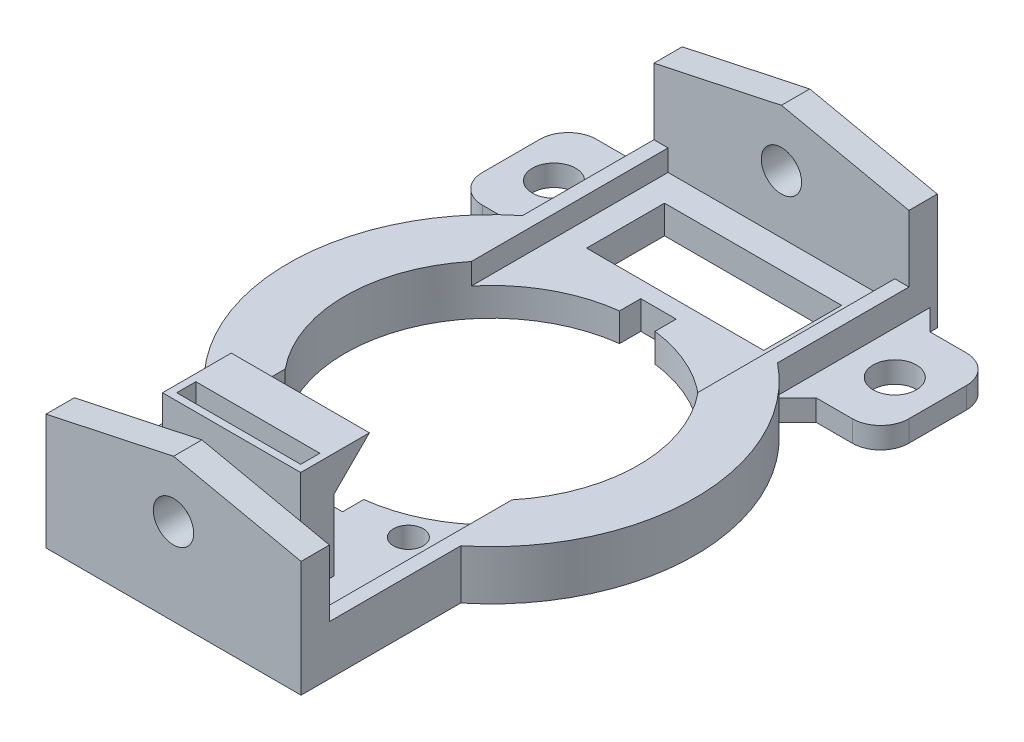
SolidWorks part; units mm, degrees
ref_plane "Front Plane" through (0, 0, 0) normal (0, 0, 1) x (1, 0, 0)
ref_plane "Top Plane" through (0, 0, 0) normal (0, 1, 0) x (1, 0, 0)
ref_plane "Right Plane" through (0, 0, 0) normal (1, 0, 0) x (0, 0, -1)
sketch "Sketch1" plane through (0, 0, 0) normal (0, 0, 1) x (1, 0, 0)
  line L3 (-18, 114.7896) -> (0, 114.7896)
  line L4 (0, 114.7896) -> (18, 114.7896)
  line L7 (0, 118.6383) -> (-38.0273, 110.5073) construction
  line L9 (38.0273, 110.5073) -> (0, 118.6383) construction
  line L11 (18, 114.7896) -> (18, 121.7896)
  line L12 (18, 121.7896) -> (16, 121.7896)
  line L13 (16, 121.7896) -> (16, 118.7896)
  line L14 (16, 118.7896) -> (-16, 118.7896)
  line L15 (-16, 118.7896) -> (-16, 121.7896)
  line L16 (-16, 121.7896) -> (-18, 121.7896)
  line L17 (-18, 121.7896) -> (-18, 114.7896)
  point P15 (0, 118.7896)
  dimension "D1" = 32
  dimension "D2" = 2
  dimension "D3" = 3
  dimension "D4" = 4
extrude "Boss-Extrude1" add sketch "Sketch1" along normal up to surface (89.8 mm away)
sketch "Sketch2" plane through (0, 114.7896, 0) normal (0, -1, 0) x (1, 0, 0)
  line L0 (18, 89.8) -> (18, 0) construction
  line L5 (-14, 54.9) -> (14, 54.9)
  line L6 (-14, 54.9) -> (-14, 34.9)
  line L7 (-14, 34.9) -> (14, 34.9)
  line L8 (14, 54.9) -> (14, 34.9)
  point P4 (0, 34.9)
  point P8 (18, 44.9)
  point P9 (14, 44.9)
  dimension "D1" = 4
  dimension "D2" = 20
extrude "Cut-Extrude1" [suppressed] cut sketch "Sketch2" against normal up to next
sketch "Sketch3" plane through (-18, 0, 0) normal (-1, 0, 0) x (0, 0, 1)
  line L0 (89.8, 121.7896) -> (0, 121.7896) construction
  line L1 (40.65, 118.7896) -> (49.15, 118.7896)
  line L2 (40.65, 118.7896) -> (40.65, 121.7896)
  line L3 (40.65, 121.7896) -> (49.15, 121.7896)
  line L4 (49.15, 118.7896) -> (49.15, 121.7896)
  line L5 (89.8, 118.7896) -> (0, 118.7896) construction
  point P9 (44.9, 121.7896)
  point P10 (44.9, 121.7896)
  dimension "D1" = 8.5
extrude "Cut-Extrude2" [suppressed] cut sketch "Sketch3" against normal through all
sketch "Sketch4" plane through (0, 118.7896, 0) normal (0, 1, 0) x (1, 0, 0)
  circle A0 centre (7.75, -23.25) radius 2.1 construction
  circle A4 centre (-7.75, -23.25) radius 2.1 construction
  circle A5 centre (7.75, -23.25) radius 2.1
  circle A6 centre (-7.75, -23.25) radius 2.1
extrude "Cut-Extrude3" [suppressed] cut sketch "Sketch4" against normal through all
ref_plane "Plane2" through (0, 0, 44.9) normal (0, 0, -1) x (-1, 0, 0)
sketch "Sketch5" plane through (0, 0, 0) normal (0, 0, 1) x (1, 0, 0)
  line L0 (-18, 114.7896) -> (-18, 131.1512)
  line L1 (-56.4, 122.9405) -> (0, 135) construction
  line L2 (-18, 131.1512) -> (0, 135)
  line L3 (0, 135) -> (18, 131.1512)
  line L4 (0, 135) -> (56.4, 122.9405) construction
  line L5 (18, 131.1512) -> (18, 114.7896)
  line L6 (18, 114.7896) -> (-18, 114.7896)
  line L7 (0.6273, 134.8659) -> (54.0273, 123.4479) construction
  line L8 (-54.0273, 123.4479) -> (-0.6273, 134.8659) construction
  circle A0 centre (0, 127) radius 2.85
  dimension "D1" = 5.7
  dimension "D2" = 8
extrude "Boss-Extrude2" add sketch "Sketch5" along normal blind 4
mirror "Mirror1" about plane through (0, 0, 44.9) normal (0, 0, -1) of "Boss-Extrude2"
sketch "Sketch6" plane through (0, 118.7896, 0) normal (0, 1, 0) x (1, 0, 0)
  line L1 (12.5, -19) -> (-12.5, -19)
  line L2 (12.5, -19) -> (12.5, -8)
  line L3 (12.5, -8) -> (-12.5, -8)
  line L4 (-12.5, -19) -> (-12.5, -8)
  point P4 (0, -8)
  dimension "D1" = 11
  dimension "D2" = 25
  dimension "D3" = 8
extrude "Cut-Extrude4" cut sketch "Sketch6" against normal through all
sketch "Sketch8" plane through (0, 118.7896, 0) normal (0, 1, 0) x (1, 0, 0)
  line L0 (16, -85.8) -> (-16, -85.8) construction
  line L1 (8.75, -80.6) -> (-8.75, -80.6)
  line L2 (8.75, -80.6) -> (8.75, -77.9)
  line L3 (8.75, -77.9) -> (-8.75, -77.9)
  line L4 (-8.75, -80.6) -> (-8.75, -77.9)
  line L5 (0, -89.8) -> (53.4, -89.8) construction
  line L6 (9.75, -76.9) -> (-9.75, -76.9)
  line L7 (-9.75, -81.6) -> (-9.75, -76.9)
  line L8 (9.75, -81.6) -> (-9.75, -81.6)
  line L9 (9.75, -81.6) -> (9.75, -76.9)
  point P6 (0, -85.8)
  point P7 (0, -80.6)
  dimension "D1" = 8.2
  dimension "D2" = 2.7
  dimension "D3" = 17.5
  dimension "D4" = 1
extrude "Boss-Extrude3" add sketch "Sketch8" along normal blind 15
sketch "Sketch9" plane through (-9.75, 0, 0) normal (-1, 0, 0) x (0, 0, 1)
  line L0 (76.9, 128.7896) -> (71.9, 133.7896)
  line L1 (76.9, 133.7896) -> (76.9, 118.7896) construction
  line L2 (71.9, 133.7896) -> (76.9, 133.7896)
  line L3 (76.9, 133.7896) -> (76.9, 128.7896)
  dimension "D1" = 5
  dimension "D2" = 45
extrude "Boss-Extrude4" add sketch "Sketch9" against normal up to surface (19.5 mm away) up to face at (9.75, 126.2896, 79.25)
sketch "Sketch13" plane through (0, 118.7896, 0) normal (0, 1, 0) x (1, 0, 0)
  line L4 (-8.75, -80.6) -> (8.75, -80.6)
  line L5 (8.75, -80.6) -> (8.75, -77.9)
  line L6 (8.75, -77.9) -> (-8.75, -77.9)
  line L7 (-8.75, -77.9) -> (-8.75, -80.6)
  line L8 (-8.75, -80.6) -> (8.75, -80.6)
  line L9 (8.75, -80.6) -> (8.75, -77.9)
  line L10 (8.75, -77.9) -> (-8.75, -77.9)
  line L11 (-8.75, -77.9) -> (-8.75, -80.6)
  dimension "D1" = 0
extrude "Cut-Extrude5" cut sketch "Sketch13" against normal through all
sketch "Sketch10" [suppressed] plane through (0, 121.7896, 0) normal (0, 1, 0) x (1, 0, 0)
  line L1 (16, -59.15) -> (18, -59.15)
  line L2 (16, -59.15) -> (16, -49.15)
  line L3 (16, -49.15) -> (18, -49.15)
  line L4 (18, -59.15) -> (18, -49.15)
  line L5 (0, -1000) -> (0, 49000) construction
  line L6 (-16, -49.15) -> (-18, -49.15)
  line L7 (-16, -59.15) -> (-16, -49.15)
  line L8 (-16, -59.15) -> (-18, -59.15)
  line L9 (-18, -59.15) -> (-18, -49.15)
  dimension "D1" = 10
extrude "Boss-Extrude5" [suppressed] add sketch "Sketch10" along normal up to surface (12 mm away)
sketch "Sketch14" plane through (0, 114.7896, 0) normal (0, 1, 0) x (1, 0, 0)
  line L0 (-18, -85.8) -> (-18, -4) construction
  line L1 (-18, -4) -> (-30.1, -4)
  line L2 (-18, -4) -> (-18, -20.1)
  line L3 (-18, -20.1) -> (-30.1, -20.1)
  line L4 (-30.1, -4) -> (-30.1, -20.1)
  circle A0 centre (-24.05, -12.05) radius 3.05
  point P9 (-30.1, -12.05)
  point P10 (-24.05, -20.1)
  dimension "D1" = 6.1
  dimension "D2" = 3
  dimension "D3" = 5
extrude "Boss-Extrude7" add sketch "Sketch14" along normal blind 3
mirror "Mirror2" about plane through (0, 0, 0) normal (1, 0, 0) of "Boss-Extrude7"
chamfer "Chamfer1" distance 3 angle 45 4 edges at (-18, 116.2896, 20.1) (-18, 116.2896, 4) (18, 116.2896, 4) (18, 116.2896, 20.1)
sketch "Sketch17" plane through (0, 118.7896, 0) normal (0, 1, 0) x (1, 0, 0)
  circle A0 centre (0, -71.9) radius 2.1
  circle A1 centre (0, -71.9) radius 2.85 construction
  dimension "D1" = 4.2
extrude "Cut-Extrude6" cut sketch "Sketch17" against normal through all
sketch "Sketch19" plane through (0, 114.7896, 0) normal (0, -1, 0) x (1, 0, 0)
  line L0 (18, 67.2537) -> (18, 55.122)
  line L2 (-16, 68.7262) -> (-16, 58.0335)
  line L3 (-18, 34.678) -> (-18, 22.5463)
  line L4 (18, 22.5463) -> (18, 34.678)
  line L6 (-18, 85.8) -> (-18, 4) construction
  line L7 (18, 85.8) -> (18, 4) construction
  line L8 (-16, 85.8) -> (-16, 4) construction
  arc A0 (-16, 58.0335) -> (-18, 34.678) centre (0, 44.9) ccw
  arc A1 (-16, 68.7262) -> (-18, 22.5463) centre (0, 44.9) ccw
  circle A2 centre (0, 44.9) radius 20.2 construction
  arc A3 (18, 22.5463) -> (18, 67.2537) centre (0, 44.9) ccw
  arc A4 (18, 34.678) -> (18, 55.122) centre (0, 44.9) ccw
  dimension "D1" = 0.5
  dimension "D2" = 8
extrude "Boss-Extrude8" add sketch "Sketch19" against normal up to surface (7 mm away) up to face at (-17, 121.7896, 44.9)
sketch "Sketch20" plane through (0, 114.7896, 0) normal (0, -1, 0) x (1, 0, 0)
  circle A0 centre (0, 44.9) radius 20.7
  arc A1 (18, 34.678) -> (18, 55.122) centre (0, 44.9) ccw construction
extrude "Cut-Extrude7" cut sketch "Sketch20" against normal through all
fillet "Fillet1" radius 4 4 edges at (-30.1, 116.2896, 4) (-30.1, 116.2896, 20.1) (30.1, 116.2896, 4) (30.1, 116.2896, 20.1)
sketch "Sketch21" plane through (0, 118.7896, 0) normal (0, 1, 0) x (1, 0, 0)
  circle A0 centre (-10.2696, -66.9233) radius 2.1 construction
  circle A1 centre (10.2696, -66.9233) radius 2.1 construction
  circle A2 centre (-10.2696, -66.9233) radius 2.1
  circle A3 centre (10.2696, -66.9233) radius 2.1
extrude "Cut-Extrude8" cut sketch "Sketch21" against normal through all
sketch "Sketch22" plane through (0, 118.7896, 0) normal (0, 1, 0) x (1, 0, 0)
  line L0 (-1000, -44.9) -> (49000, -44.9) construction
  line L1 (-2.5, -65.4485) -> (2.5, -65.4485)
  line L2 (-2.5, -65.4485) -> (-2.5, -68.4485)
  line L3 (-2.5, -68.4485) -> (2.5, -68.4485)
  line L4 (2.5, -65.4485) -> (2.5, -68.4485)
  line L5 (2.5, -24.3515) -> (2.5, -21.3515)
  line L6 (-2.5, -21.3515) -> (2.5, -21.3515)
  line L7 (-2.5, -24.3515) -> (-2.5, -21.3515)
  line L8 (-2.5, -24.3515) -> (2.5, -24.3515)
  arc A0 (-16, -58.0335) -> (16, -58.0335) centre (0, -44.9) ccw construction
  dimension "D1" = 5
  dimension "D2" = 3
extrude "Cut-Extrude9" cut sketch "Sketch22" against normal through all
equation "\"width\"= 24"
equation "\"thk\"= 3"
equation "\"holesize\"= 4.2"
equation "\"holedistance\"= ( 20 + 12 ) / 2"
equation "\"threaded_hole\"= 3.9"
equation "\"fillet_radius\"= 2"
equation "\"ground_clearance\"= 25"
equation "\"tire_thk\"= 3"
equation "\"innerwheel_diam\" = \"wheel_diam\"-2*\"tire_thk\""
equation "\"innerwheel_thk\"= 8"
equation "\"wheel_diam\"= 2*(\"width\"/2+\"ground_clearance\")"
equation "\"coloursensor_holesize\"= 2.65"
equation "\"hole_to_edge\" = 4"
equation "\"D1@Sketch5\"=\"M4_insert_diam\""
equation "\"D1@Sketch17\"=\"holesize\""
equation "\"M4_insert_diam\"= 5.7"
